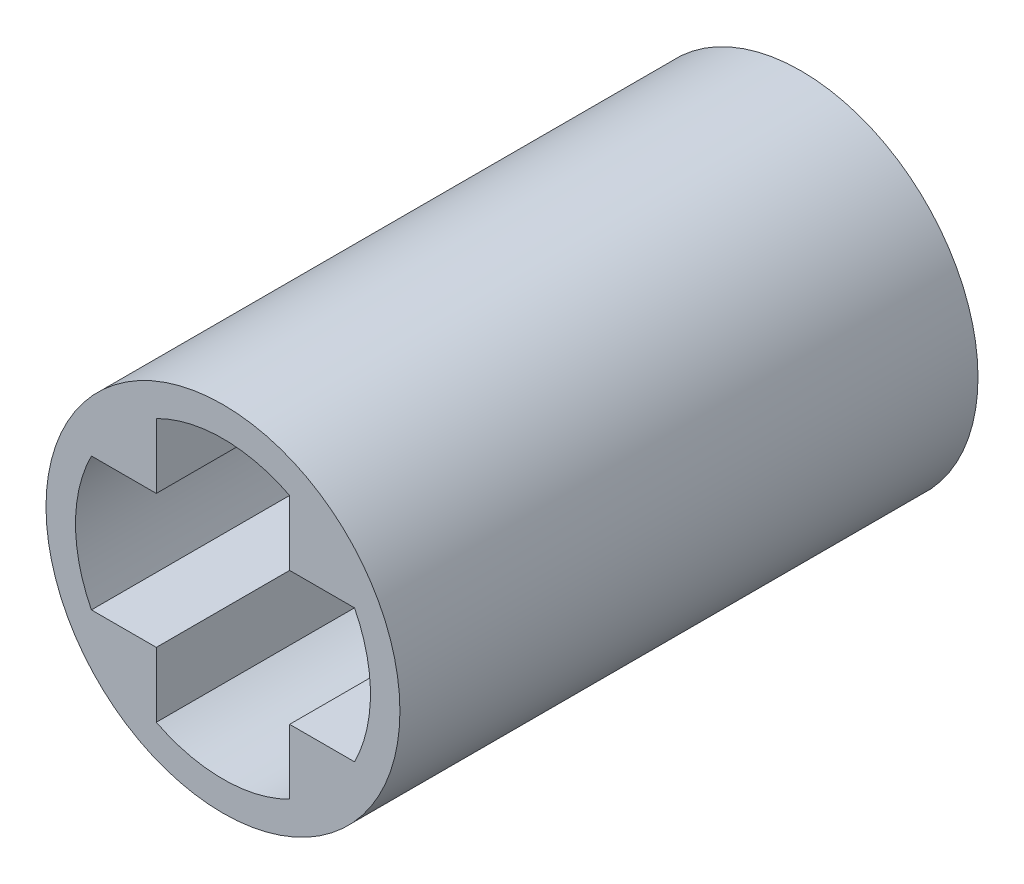
SolidWorks part; units mm, degrees
ref_plane "前视基准面" through (0, 0, 0) normal (0, 0, 1) x (1, 0, 0)
ref_plane "上视基准面" through (0, 0, 0) normal (0, 1, 0) x (1, 0, 0)
ref_plane "右视基准面" through (0, 0, 0) normal (1, 0, 0) x (0, 0, -1)
other "Configuration Table"
sketch "草图1" plane through (0, 0, 0) normal (0, 0, 1) x (1, 0, 0)
  line L0 (0, 0) -> (1.6518, 0.578) construction
  line L1 (0, 0) -> (1.5463, 0.5596)
  line L2 (0, 0) -> (1.5463, -0.5596)
  line L3 (0, 0) -> (1.6518, -0.578) construction
  line L4 (0, 0) -> (2.5312, 0) construction
  line L5 (1.6518, 0.578) -> (1.6518, -0.578) construction
  circle A0 centre (0, 0) radius 1.4062
  circle A1 centre (0, 0) radius 2.5312
  circle A2 centre (0, 0) radius 1.6445 construction
  circle A3 centre (0, 0) radius 1.75 construction
  circle A4 centre (0, 0) radius 3
  spline S0 degree 4 poles (1.5463, 0.5596) (1.5581, 0.5639) (1.5919, 0.5732) (1.6587, 0.581) (1.7677, 0.5785) (1.907, 0.5533) (2.0794, 0.496) (2.2692, 0.3992) (2.4603, 0.2642) (2.6441, 0.0916) (2.8051, -0.1022) (2.943, -0.313) (3.064, -0.5479) (3.1824, -0.853) (3.2764, -1.2324) (3.3196, -1.6847) (3.2901, -2.1883) (3.1874, -2.6826) (3.0209, -3.1576) (2.7922, -3.6086) (2.5154, -4.0264) (2.1841, -4.4125) (1.8255, -4.754) (1.409, -5.0644) (1.076, -5.2702) (0.6819, -5.4662) (0.4502, -5.5624) (0.1823, -5.6645) (0.044, -5.7026) (-0.0764, -5.7409) (-0.1139, -5.7494) (-0.1402, -5.7568) (-0.1543, -5.7609) knots 0 0 0 0 0 0.005604 0.015718 0.02996 0.048734 0.068727 0.096889 0.125051 0.153212 0.181374 0.209535 0.237696 0.271429 0.327752 0.384075 0.440398 0.496721 0.553044 0.609367 0.66569 0.722013 0.778336 0.834659 0.890982 0.909091 0.954545 0.977273 0.988636 0.994318 1 1 1 1 1 construction
  spline S1 degree 4 poles (1.5463, 0.5596) (1.5581, 0.5639) (1.5919, 0.5732) (1.6587, 0.581) (1.7677, 0.5785) (1.907, 0.5533) (2.0794, 0.496) (2.2692, 0.3992) (2.4603, 0.2642) (2.6441, 0.0916) (2.8051, -0.1022) (2.943, -0.313) (3.064, -0.5479) (3.1824, -0.853) (3.2764, -1.2324) (3.3196, -1.6847) (3.2901, -2.1883) (3.1874, -2.6826) (3.0209, -3.1576) (2.7922, -3.6086) (2.5154, -4.0264) (2.1841, -4.4125) (1.8255, -4.754) (1.409, -5.0644) (1.076, -5.2702) (0.7836, -5.4156) (0.6453, -5.4782) (0.6117, -5.493) knots 0 0 0 0 0 0.005604 0.015718 0.02996 0.048734 0.068727 0.096889 0.125051 0.153212 0.181374 0.209535 0.237696 0.271429 0.327752 0.384075 0.440398 0.496721 0.553044 0.609367 0.66569 0.722013 0.778336 0.834659 0.890982 0.909091 0.909091 0.909091 0.909091 0.909091
  spline S2 degree 4 poles (1.5463, -0.5596) (1.5581, -0.5639) (1.5919, -0.5732) (1.6587, -0.581) (1.7677, -0.5785) (1.907, -0.5533) (2.0794, -0.496) (2.2692, -0.3992) (2.4603, -0.2642) (2.6441, -0.0916) (2.8051, 0.1022) (2.943, 0.313) (3.064, 0.5479) (3.1824, 0.853) (3.2764, 1.2324) (3.3196, 1.6847) (3.2901, 2.1883) (3.1874, 2.6826) (3.0209, 3.1576) (2.7922, 3.6086) (2.5154, 4.0264) (2.1841, 4.4125) (1.8255, 4.754) (1.409, 5.0644) (1.076, 5.2702) (0.6819, 5.4662) (0.4502, 5.5624) (0.1823, 5.6645) (0.044, 5.7026) (-0.0764, 5.7409) (-0.1139, 5.7494) (-0.1402, 5.7568) (-0.1543, 5.7609) knots 0 0 0 0 0 0.005604 0.015718 0.02996 0.048734 0.068727 0.096889 0.125051 0.153212 0.181374 0.209535 0.237696 0.271429 0.327752 0.384075 0.440398 0.496721 0.553044 0.609367 0.66569 0.722013 0.778336 0.834659 0.890982 0.909091 0.954545 0.977273 0.988636 0.994318 1 1 1 1 1 construction
  spline S3 degree 4 poles (1.5463, -0.5596) (1.5581, -0.5639) (1.5919, -0.5732) (1.6587, -0.581) (1.7677, -0.5785) (1.907, -0.5533) (2.0794, -0.496) (2.2692, -0.3992) (2.4603, -0.2642) (2.6441, -0.0916) (2.8051, 0.1022) (2.943, 0.313) (3.064, 0.5479) (3.1824, 0.853) (3.2764, 1.2324) (3.3196, 1.6847) (3.2901, 2.1883) (3.1874, 2.6826) (3.0209, 3.1576) (2.7922, 3.6086) (2.5154, 4.0264) (2.1841, 4.4125) (1.8255, 4.754) (1.409, 5.0644) (1.076, 5.2702) (0.7836, 5.4156) (0.6453, 5.4782) (0.6117, 5.493) knots 0 0 0 0 0 0.005604 0.015718 0.02996 0.048734 0.068727 0.096889 0.125051 0.153212 0.181374 0.209535 0.237696 0.271429 0.327752 0.384075 0.440398 0.496721 0.553044 0.609367 0.66569 0.722013 0.778336 0.834659 0.890982 0.909091 0.909091 0.909091 0.909091 0.909091
  point P16 (1.6518, 0)
  dimension "内啮合齿顶圆直径" = 2.8125
  dimension "内啮合分度圆直径" = 3.5
  dimension "内啮合基圆直径" = 3.2889
  dimension "内啮合齿根圆直径" = 5.0625
  dimension "外径" = 6
  dimension "渐开线镜像线夹角" = 19.286
extrude "凸台-拉伸1" add sketch "草图1" along normal blind 5 contours A4 | A0
extrude "切除-拉伸2" cut sketch "草图1<3>" along normal through all contours A0 S3 A1 S1 region at (1.8886, 0, 0)
sketch "草图1<3>" plane through (0, 0, 0) normal (0, 0, 1) x (1, 0, 0) same geometry as "草图1"
pattern_circular "阵列(圆周)1" count 7 over 360 about axis through (0, 0, 5) along (0, 0, 1) of "切除-拉伸2"
sketch "草图2" plane through (0, 0, 5) normal (0, 0, 1) x (1, 0, 0)
  line L1 (-1.13, 2.23) -> (1.13, 2.23)
  line L2 (-1.13, 2.23) -> (-1.13, -2.23)
  line L3 (-1.13, -2.23) -> (1.13, -2.23)
  line L4 (1.13, 2.23) -> (1.13, -2.23)
  line L5 (-1.13, 2.23) -> (1.13, -2.23) construction
  line L6 (-1.13, -2.23) -> (1.13, 2.23) construction
  line L7 (-2.23, -1.13) -> (2.23, -1.13)
  line L8 (-2.23, -1.13) -> (-2.23, 1.13)
  line L9 (-2.23, 1.13) -> (2.23, 1.13)
  line L10 (2.23, -1.13) -> (2.23, 1.13)
  line L11 (-2.23, -1.13) -> (2.23, 1.13) construction
  line L12 (-2.23, 1.13) -> (2.23, -1.13) construction
  circle A0 centre (0, 0) radius 3
  circle A1 centre (0, 0) radius 3 construction
  circle A3 centre (0, 0) radius 2.5
  point P5 (0, 0)
  point P10 (0, 0)
  point P16 (0, 0)
  point P18 (0, 0)
  point P19 (0, 0)
  spline M7 degree 4 poles (0.2015, -1.6321) (0.203, -1.6445) (0.2046, -1.6796) (0.1973, -1.7464) (0.1706, -1.8521) (0.1151, -1.9823) (0.0209, -2.1377) (-0.1157, -2.3012) (-0.2899, -2.4574) (-0.4991, -2.5982) (-0.7238, -2.712) (-0.96, -2.7996) (-1.216, -2.8652) (-1.5398, -2.9128) (-1.9305, -2.92) (-2.3812, -2.8615) (-2.8655, -2.7207) (-3.3246, -2.5106) (-3.7507, -2.2425) (-4.1394, -1.9192) (-4.4852, -1.5564) (-4.7878, -1.1474) (-5.041, -0.7219) (-5.251, -0.2468) (-5.3775, 0.1237) (-5.4542, 0.4412) (-5.4844, 0.5898) (-5.4914, 0.6259) knots 0 0 0 0 0 0.005604 0.015718 0.02996 0.048734 0.068727 0.096889 0.125051 0.153212 0.181374 0.209535 0.237696 0.271429 0.327752 0.384075 0.440398 0.496721 0.553044 0.609367 0.66569 0.722013 0.778336 0.834659 0.890982 0.909091 0.909091 0.909091 0.909091 0.909091 only from (0.2015, -1.6321) to (-0.3659, -2.5047)
  spline M9 degree 4 poles (5.2191, -1.8187) (5.1972, -1.8482) (5.1055, -1.969) (4.8986, -2.2218) (4.6239, -2.5006) (4.2285, -2.8376) (3.8158, -3.1112) (3.3657, -3.3483) (2.8968, -3.5251) (2.4063, -3.6478) (1.9061, -3.7044) (1.4013, -3.6946) (0.9038, -3.6112) (0.4724, -3.4685) (0.1235, -3.2925) (-0.1476, -3.1091) (-0.3498, -2.9389) (-0.5245, -2.7575) (-0.6777, -2.5574) (-0.805, -2.3398) (-0.8942, -2.1235) (-0.9463, -1.9169) (-0.9638, -1.7361) (-0.9573, -1.5947) (-0.9355, -1.4879) (-0.9131, -1.4245) (-0.8964, -1.3936) (-0.8897, -1.383) knots 0 0 0 0 0 0.018109 0.074432 0.130755 0.187078 0.243401 0.299724 0.356047 0.41237 0.468693 0.525016 0.581339 0.637662 0.671395 0.699556 0.727717 0.755879 0.78404 0.812202 0.840364 0.860357 0.879131 0.893373 0.903487 0.909091 0.909091 0.909091 0.909091 0.909091 only from (-0.7571, -2.4154) to (-0.8897, -1.383)
  spline M15 degree 4 poles (1.8322, -5.2144) (1.7955, -5.2157) (1.6438, -5.2193) (1.3172, -5.2151) (0.9279, -5.1742) (0.4179, -5.0752) (-0.0533, -4.9231) (-0.5193, -4.7191) (-0.95, -4.4627) (-1.3517, -4.1556) (-1.7078, -3.7999) (-2.0148, -3.3991) (-2.2598, -2.9582) (-2.4172, -2.5319) (-2.4972, -2.1493) (-2.5228, -1.8231) (-2.5158, -1.5589) (-2.4829, -1.3092) (-2.422, -1.0647) (-2.3313, -0.8294) (-2.2177, -0.6249) (-2.0887, -0.4553) (-1.9582, -0.3289) (-1.8437, -0.2458) (-1.7465, -0.1963) (-1.683, -0.1743) (-1.6485, -0.168) (-1.636, -0.1667) knots 0 0 0 0 0 0.018109 0.074432 0.130755 0.187078 0.243401 0.299724 0.356047 0.41237 0.468693 0.525016 0.581339 0.637662 0.671395 0.699556 0.727717 0.755879 0.78404 0.812202 0.840364 0.860357 0.879131 0.893373 0.903487 0.909091 0.909091 0.909091 0.909091 0.909091 only from (-2.3605, -0.914) to (-1.636, -0.1667)
  spline M19 degree 4 poles (-1.636, 0.1667) (-1.6485, 0.168) (-1.683, 0.1743) (-1.7465, 0.1963) (-1.8437, 0.2458) (-1.9582, 0.3289) (-2.0887, 0.4553) (-2.2177, 0.6249) (-2.3313, 0.8294) (-2.422, 1.0647) (-2.4829, 1.3092) (-2.5158, 1.5589) (-2.5228, 1.8231) (-2.4972, 2.1493) (-2.4172, 2.5319) (-2.2598, 2.9582) (-2.0148, 3.3991) (-1.7078, 3.7999) (-1.3517, 4.1556) (-0.95, 4.4627) (-0.5193, 4.7191) (-0.0533, 4.9231) (0.4179, 5.0752) (0.9279, 5.1742) (1.3172, 5.2151) (1.6438, 5.2193) (1.7955, 5.2157) (1.8322, 5.2144) knots 0 0 0 0 0 0.005604 0.015718 0.02996 0.048734 0.068727 0.096889 0.125051 0.153212 0.181374 0.209535 0.237696 0.271429 0.327752 0.384075 0.440398 0.496721 0.553044 0.609367 0.66569 0.722013 0.778336 0.834659 0.890982 0.909091 0.909091 0.909091 0.909091 0.909091 only from (-1.636, 0.1667) to (-2.3605, 0.914)
  spline M25 degree 4 poles (-0.8897, 1.383) (-0.8964, 1.3936) (-0.9131, 1.4245) (-0.9355, 1.4879) (-0.9573, 1.5947) (-0.9638, 1.7361) (-0.9463, 1.9169) (-0.8942, 2.1235) (-0.805, 2.3398) (-0.6777, 2.5574) (-0.5245, 2.7575) (-0.3498, 2.9389) (-0.1476, 3.1091) (0.1235, 3.2925) (0.4724, 3.4685) (0.9038, 3.6112) (1.4013, 3.6946) (1.9061, 3.7044) (2.4063, 3.6478) (2.8968, 3.5251) (3.3657, 3.3483) (3.8158, 3.1112) (4.2285, 2.8376) (4.6239, 2.5006) (4.8986, 2.2218) (5.1055, 1.969) (5.1972, 1.8482) (5.2191, 1.8187) knots 0 0 0 0 0 0.005604 0.015718 0.02996 0.048734 0.068727 0.096889 0.125051 0.153212 0.181374 0.209535 0.237696 0.271429 0.327752 0.384075 0.440398 0.496721 0.553044 0.609367 0.66569 0.722013 0.778336 0.834659 0.890982 0.909091 0.909091 0.909091 0.909091 0.909091 only from (-0.8897, 1.383) to (-0.7571, 2.4154)
  spline M27 degree 4 poles (-5.4914, -0.6259) (-5.4844, -0.5898) (-5.4542, -0.4412) (-5.3775, -0.1237) (-5.251, 0.2468) (-5.041, 0.7219) (-4.7878, 1.1474) (-4.4852, 1.5564) (-4.1394, 1.9192) (-3.7507, 2.2425) (-3.3246, 2.5106) (-2.8655, 2.7207) (-2.3812, 2.8615) (-1.9305, 2.92) (-1.5398, 2.9128) (-1.216, 2.8652) (-0.96, 2.7996) (-0.7238, 2.712) (-0.4991, 2.5982) (-0.2899, 2.4574) (-0.1157, 2.3012) (0.0209, 2.1377) (0.1151, 1.9823) (0.1706, 1.8521) (0.1973, 1.7464) (0.2046, 1.6796) (0.203, 1.6445) (0.2015, 1.6321) knots 0 0 0 0 0 0.018109 0.074432 0.130755 0.187078 0.243401 0.299724 0.356047 0.41237 0.468693 0.525016 0.581339 0.637662 0.671395 0.699556 0.727717 0.755879 0.78404 0.812202 0.840364 0.860357 0.879131 0.893373 0.903487 0.909091 0.909091 0.909091 0.909091 0.909091 only from (-0.3659, 2.5047) to (0.2015, 1.6321)
  spline M37 degree 4 poles (1.5463, 0.5596) (1.5581, 0.5639) (1.5919, 0.5732) (1.6587, 0.581) (1.7677, 0.5785) (1.907, 0.5533) (2.0794, 0.496) (2.2692, 0.3992) (2.4603, 0.2642) (2.6441, 0.0916) (2.8051, -0.1022) (2.943, -0.313) (3.064, -0.5479) (3.1824, -0.853) (3.2764, -1.2324) (3.3196, -1.6847) (3.2901, -2.1883) (3.1874, -2.6826) (3.0209, -3.1576) (2.7922, -3.6086) (2.5154, -4.0264) (2.1841, -4.4125) (1.8255, -4.754) (1.409, -5.0644) (1.076, -5.2702) (0.7836, -5.4156) (0.6453, -5.4782) (0.6117, -5.493) knots 0 0 0 0 0 0.005604 0.015718 0.02996 0.048734 0.068727 0.096889 0.125051 0.153212 0.181374 0.209535 0.237696 0.271429 0.327752 0.384075 0.440398 0.496721 0.553044 0.609367 0.66569 0.722013 0.778336 0.834659 0.890982 0.909091 0.909091 0.909091 0.909091 0.909091 only from (1.5463, 0.5596) to (2.5233, 0.2007)
  spline M39 degree 4 poles (0.6117, 5.493) (0.6453, 5.4782) (0.7836, 5.4156) (1.076, 5.2702) (1.409, 5.0644) (1.8255, 4.754) (2.1841, 4.4125) (2.5154, 4.0264) (2.7922, 3.6086) (3.0209, 3.1576) (3.1874, 2.6826) (3.2901, 2.1883) (3.3196, 1.6847) (3.2764, 1.2324) (3.1824, 0.853) (3.064, 0.5479) (2.943, 0.313) (2.8051, 0.1022) (2.6441, -0.0916) (2.4603, -0.2642) (2.2692, -0.3992) (2.0794, -0.496) (1.907, -0.5533) (1.7677, -0.5785) (1.6587, -0.581) (1.5919, -0.5732) (1.5581, -0.5639) (1.5463, -0.5596) knots 0 0 0 0 0 0.018109 0.074432 0.130755 0.187078 0.243401 0.299724 0.356047 0.41237 0.468693 0.525016 0.581339 0.637662 0.671395 0.699556 0.727717 0.755879 0.78404 0.812202 0.840364 0.860357 0.879131 0.893373 0.903487 0.909091 0.909091 0.909091 0.909091 0.909091 only from (2.5233, -0.2007) to (1.5463, -0.5596)
  dimension "D1" = 5
  dimension "D2" = 1.1
extrude "凸台-拉伸2" add sketch "草图2" along normal blind 4.8 contours A0
extrude "切除-拉伸3" cut sketch "草图2<4>" against normal offset from surface (3.8 mm away) 1 from surface contours L1 A3 M27 | A3 L1 M27 M25 | A3 L1 M25 | A3 L8 M19 M15 | L8 A3 M19 | A3 L8 M15 | A3 L3 M7 | A3 L3 M9 M7 | L3 A3 M9 | A3 L10 M37 | A3 L10 M39 M37 | L10 A3 M39 | L2 L3 L4 L1 | L7 L10 L9 L8 region at (0, 2.3385, 5) region at (-2.3385, 0, 5) region at (2.3385, 0, 5) region at (0, -2.3385, 5) up to face at (0, 0, 5) starting at face at (3, 0, 9.8)
sketch "草图2<4>" plane through (0, 0, 5) normal (0, 0, 1) x (1, 0, 0) same geometry as "草图2"
equation "\"m\"= 0.5'模数"
equation "\"z1\"= 7'外啮合齿轮数"
equation "\"a\"= 20度'压力角"
equation "\"z2\"= 7'内啮合齿轮数"
equation "\"hax\"= 1'齿顶高系数"
equation "\"cx\"= 0.25'顶隙系数"
equation "\"ha\"= \"hax\" * \"m\"'齿顶高"
equation "\"hf\"= ( \"hax\" + \"cx\" ) * \"m\"'齿根高"
equation "\"d1\"= \"m\" * \"z1\"'外啮合分度圆直径"
equation "\"da1\"= ( \"z1\" + 2 ) * \"m\"'外啮合齿顶圆直径"
equation "\"df1\"= \"d1\" - 2 * \"hf\"'外啮合齿根圆直径"
equation "\"db1\"= \"d1\" * cos ( \"a\" )'外啮合基圆直径"
equation "\"p\"= \"m\" * PI'齿距"
equation "\"d2\"= \"m\" * \"z2\"'内啮合分度圆直径"
equation "\"db2\"= \"d2\" * cos ( \"a\" )'内啮合基圆直径"
equation "\"da2\"= ( \"z2\" - 2 ) * \"m\"'内啮合齿顶圆直径"
equation "\"df2\"= \"d2\" + 2 * \"hf\"'内啮合齿根圆直径"
equation "\"内啮合齿顶圆直径@草图1\" = \"da2\" + 0.5 * \"hf\""
equation "\"内啮合齿根圆直径@草图1\"= \"df2\" + 0.5 * \"hf\""
equation "\"内啮合分度圆直径@草图1\"= \"d2\""
equation "\"内啮合基圆直径@草图1\"= \"db2\""
equation "\"渐开线镜像线夹角@草图1\"= 360度 / 4 / \"z2\" + 360度 / 4 / \"z2\" / 2"
equation "\"do\"= IIF ( \"edo\" >= ( \"df2\" + 1 ) , \"edo\" , ( \"df2\" + 1 ) )'外圈直径"
equation "\"h\"= 5'厚度"
equation "\"外径@草图1\"= \"do\""
equation "\"厚度@凸台-拉伸1\"= \"h\""
equation "\"内啮合齿轮数@阵列(圆周)1\"= \"z2\""
equation "\"edo\"= 6'期望的外圈直径"
